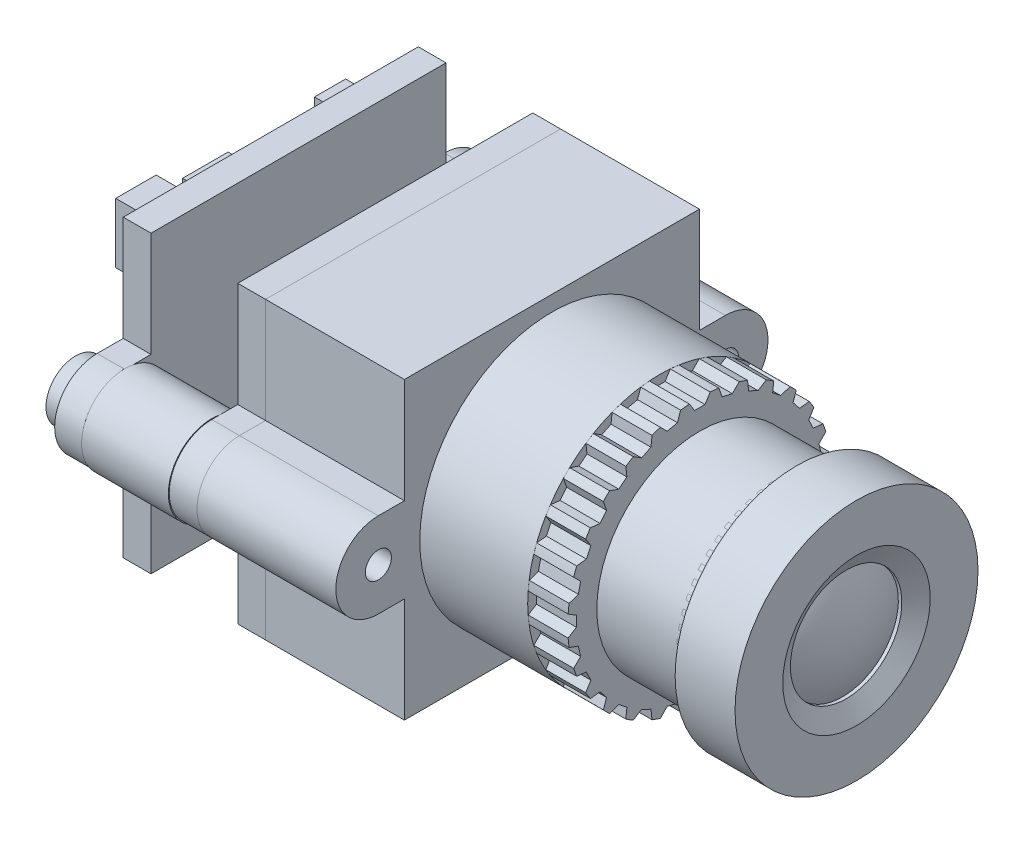
SolidWorks part; units mm, degrees
ref_plane "Front Plane" through (0, 0, 0) normal (0, 0, 1) x (1, 0, 0)
ref_plane "Top Plane" through (0, 0, 0) normal (0, 1, 0) x (1, 0, 0)
ref_plane "Right Plane" through (0, 0, 0) normal (1, 0, 0) x (0, 0, -1)
ref_axis "Axis1" through (-11.8965, 0, 0) along (1, 0, 0)
sketch "Sketch1" plane through (0, 0, 0) normal (1, 0, 0) x (0, 0, -1)
  circle A0 centre (0, 0) radius 7
  dimension "D1" = 14
extrude "Boss-Extrude1" add sketch "Sketch1" against normal blind 3.45
sketch "Sketch2" plane through (-3.45, 0, 0) normal (-1, 0, 0) x (0, 0, 1)
  circle A0 centre (0, 0) radius 5.935
  dimension "D1" = 11.87
extrude "Boss-Extrude2" add sketch "Sketch2" along normal blind 5.58
sketch "Sketch3" plane through (-9.03, 0, 0) normal (-1, 0, 0) x (0, 0, 1)
  circle A0 centre (0, 0) radius 7.61
  dimension "D1" = 15.22
extrude "Boss-Extrude3" add sketch "Sketch3" along normal blind 2.3
sketch "Sketch4" plane through (0, 0, 0) normal (0, 0, 1) x (1, 0, 0)
  line L0 (-3.45, 0) -> (0, 0) construction
  line L1 (-3.45, 5.935) -> (-3.45, -5.935) construction
  line L2 (0, -7) -> (0, 7) construction
  line L3 (0, 7) -> (-3.45, 7) construction
  line L4 (-0.6, 4.25) -> (0, 4.25)
  line L5 (-0.6, 4.25) -> (-0.6, -4.25)
  line L6 (-0.6, -4.25) -> (0, -4.25)
  line L7 (0, 4.25) -> (0, -4.25)
  line L8 (-0.6, 4.25) -> (0, -4.25) construction
  line L9 (-0.6, -4.25) -> (0, 4.25) construction
  line L10 (0, 4.25) -> (-0.6, 3.2108)
  line L11 (-0.8, 0) -> (-0.6, 3.2108) construction
  line L12 (-0.8, -3.2108) -> (-0.6, -3.2108)
  line L13 (-0.8, -3.2108) -> (-0.8, 3.2108)
  line L14 (-0.8, 3.2108) -> (-0.6, 3.2108)
  line L15 (-0.6, -3.2108) -> (-0.6, 3.2108)
  line L16 (-0.8, -3.2108) -> (-0.6, 3.2108) construction
  line L17 (-0.8, 3.2108) -> (-0.6, -3.2108) construction
  line L18 (-0.7, 1.6054) -> (0, 1.6054) construction
  line L19 (-0.8, 0) -> (0, 0)
  line L21 (0, 0) -> (0.6, 0)
  line L22 (0, 0) -> (0, 4.25)
  line L23 (0, 4.25) -> (0.6, 4.25)
  line L24 (0.6, 0) -> (0.6, 4.25)
  spline S0 degree 2 poles (0, 0) (0, 1.7034) (-0.8, 3.2108) knots 0 0 0 1 1 1
  point P6 (-0.3, 0)
  point P15 (-0.7, 0)
  dimension "D1" = 0.6
  dimension "D2" = 2.75
  dimension "D3" = 60
  dimension "D4" = 0.2
  dimension "D5" = 0.6
revolve "Cut-Revolve7" cut sketch "Sketch4" angle 360 about axis through (-11.8965, 0, 0) along (1, 0, 0) region at (0.3, 2.125, 0) region at (-0.2115, 2.72, 0) region at (-0.6658, 3.0768, 0)
sketch "Sketch5" plane through (-9.03, 0, 0) normal (1, 0, 0) x (0, 0, -1)
  line L0 (0, 7.61) -> (0, -7.61) construction
  line L1 (0.6, 7.5863) -> (0.3, 7.11)
  line L2 (0.3, 7.11) -> (-0.3, 7.11)
  line L3 (-0.6, 7.5863) -> (-0.3, 7.11)
  line L4 (2.2731, 7.2626) -> (1.8746, 6.865)
  line L5 (1.8746, 6.865) -> (1.2896, 6.9985)
  line L6 (1.1032, 7.5296) -> (1.2896, 6.9985)
  line L7 (3.8322, 6.5747) -> (3.3552, 6.2757)
  line L8 (3.3552, 6.2757) -> (2.8146, 6.5361)
  line L9 (2.751, 7.0954) -> (2.8146, 6.5361)
  line L10 (5.1991, 5.5571) -> (4.6676, 5.3718)
  line L11 (4.6676, 5.3718) -> (4.1985, 5.7459)
  line L12 (4.2609, 6.3053) -> (4.1985, 5.7459)
  line L13 (6.3053, 4.2609) -> (5.7459, 4.1985)
  line L14 (5.7459, 4.1985) -> (5.3718, 4.6676)
  line L15 (5.5571, 5.1991) -> (5.3718, 4.6676)
  line L16 (7.0954, 2.751) -> (6.5361, 2.8146)
  line L17 (6.5361, 2.8146) -> (6.2757, 3.3552)
  line L18 (6.5747, 3.8322) -> (6.2757, 3.3552)
  line L19 (7.5296, 1.1032) -> (6.9985, 1.2896)
  line L20 (6.9985, 1.2896) -> (6.865, 1.8746)
  line L21 (7.2626, 2.2731) -> (6.865, 1.8746)
  line L22 (7.5863, -0.6) -> (7.11, -0.3)
  line L23 (7.11, -0.3) -> (7.11, 0.3)
  line L24 (7.5863, 0.6) -> (7.11, 0.3)
  line L25 (7.2626, -2.2731) -> (6.865, -1.8746)
  line L26 (6.865, -1.8746) -> (6.9985, -1.2896)
  line L27 (7.5296, -1.1032) -> (6.9985, -1.2896)
  line L28 (6.5747, -3.8322) -> (6.2757, -3.3552)
  line L29 (6.2757, -3.3552) -> (6.5361, -2.8146)
  line L30 (7.0954, -2.751) -> (6.5361, -2.8146)
  line L31 (5.5571, -5.1991) -> (5.3718, -4.6676)
  line L32 (5.3718, -4.6676) -> (5.7459, -4.1985)
  line L33 (6.3053, -4.2609) -> (5.7459, -4.1985)
  line L34 (4.2609, -6.3053) -> (4.1985, -5.7459)
  line L35 (4.1985, -5.7459) -> (4.6676, -5.3718)
  line L36 (5.1991, -5.5571) -> (4.6676, -5.3718)
  line L37 (2.751, -7.0954) -> (2.8146, -6.5361)
  line L38 (2.8146, -6.5361) -> (3.3552, -6.2757)
  line L39 (3.8322, -6.5747) -> (3.3552, -6.2757)
  line L40 (1.1032, -7.5296) -> (1.2896, -6.9985)
  line L41 (1.2896, -6.9985) -> (1.8746, -6.865)
  line L42 (2.2731, -7.2626) -> (1.8746, -6.865)
  line L43 (-0.6, -7.5863) -> (-0.3, -7.11)
  line L44 (-0.3, -7.11) -> (0.3, -7.11)
  line L45 (0.6, -7.5863) -> (0.3, -7.11)
  line L46 (-2.2731, -7.2626) -> (-1.8746, -6.865)
  line L47 (-1.8746, -6.865) -> (-1.2896, -6.9985)
  line L48 (-1.1032, -7.5296) -> (-1.2896, -6.9985)
  line L49 (-3.8322, -6.5747) -> (-3.3552, -6.2757)
  line L50 (-3.3552, -6.2757) -> (-2.8146, -6.5361)
  line L51 (-2.751, -7.0954) -> (-2.8146, -6.5361)
  line L52 (-5.1991, -5.5571) -> (-4.6676, -5.3718)
  line L53 (-4.6676, -5.3718) -> (-4.1985, -5.7459)
  line L54 (-4.2609, -6.3053) -> (-4.1985, -5.7459)
  line L55 (-6.3053, -4.2609) -> (-5.7459, -4.1985)
  line L56 (-5.7459, -4.1985) -> (-5.3718, -4.6676)
  line L57 (-5.5571, -5.1991) -> (-5.3718, -4.6676)
  line L58 (-7.0954, -2.751) -> (-6.5361, -2.8146)
  line L59 (-6.5361, -2.8146) -> (-6.2757, -3.3552)
  line L60 (-6.5747, -3.8322) -> (-6.2757, -3.3552)
  line L61 (-7.5296, -1.1032) -> (-6.9985, -1.2896)
  line L62 (-6.9985, -1.2896) -> (-6.865, -1.8746)
  line L63 (-7.2626, -2.2731) -> (-6.865, -1.8746)
  line L64 (-7.5863, 0.6) -> (-7.11, 0.3)
  line L65 (-7.11, 0.3) -> (-7.11, -0.3)
  line L66 (-7.5863, -0.6) -> (-7.11, -0.3)
  line L67 (-7.2626, 2.2731) -> (-6.865, 1.8746)
  line L68 (-6.865, 1.8746) -> (-6.9985, 1.2896)
  line L69 (-7.5296, 1.1032) -> (-6.9985, 1.2896)
  line L70 (-6.5747, 3.8322) -> (-6.2757, 3.3552)
  line L71 (-6.2757, 3.3552) -> (-6.5361, 2.8146)
  line L72 (-7.0954, 2.751) -> (-6.5361, 2.8146)
  line L73 (-5.5571, 5.1991) -> (-5.3718, 4.6676)
  line L74 (-5.3718, 4.6676) -> (-5.7459, 4.1985)
  line L75 (-6.3053, 4.2609) -> (-5.7459, 4.1985)
  line L76 (-4.2609, 6.3053) -> (-4.1985, 5.7459)
  line L77 (-4.1985, 5.7459) -> (-4.6676, 5.3718)
  line L78 (-5.1991, 5.5571) -> (-4.6676, 5.3718)
  line L79 (-2.751, 7.0954) -> (-2.8146, 6.5361)
  line L80 (-2.8146, 6.5361) -> (-3.3552, 6.2757)
  line L81 (-3.8322, 6.5747) -> (-3.3552, 6.2757)
  line L82 (-1.1032, 7.5296) -> (-1.2896, 6.9985)
  line L83 (-1.2896, 6.9985) -> (-1.8746, 6.865)
  line L84 (-2.2731, 7.2626) -> (-1.8746, 6.865)
  circle A0 centre (0, 0) radius 7.61 construction
  circle A1 centre (0, 0) radius 7.61 construction
  circle A2 centre (0, 0) radius 7.61
  point P12 (0, 7.11)
  point P123 (0, 0)
  circle M6 centre (0, 0) radius 7.61
  dimension "D1" = 0.6
  dimension "D2" = 1.2
  dimension "D3" = 0.5
  dimension "D5" = 0.5063
  dimension "D4" = 28
extrude "Cut-Extrude1" cut sketch "Sketch5" against normal up to next (2.3 mm away) contours L9 L8 L7 M6 | L6 L5 L4 M6 | L0 L2 L1 M6 | L84 L83 L82 M6 | L0 A2 L3 L2 | L81 L80 L79 M6 | L78 L77 L76 M6 | L75 L74 L73 M6 | L72 L71 L70 M6 | L69 L68 L67 M6 | L66 L65 L64 M6 | L63 L62 L61 M6 | L60 L59 L58 M6 | L57 L56 L55 M6 | L51 L50 L49 M6 | L54 L53 L52 M6 | L48 L47 L46 M6 | L0 L44 L43 M6 | L44 L0 A2 L45 | L42 L41 L40 M6 | L39 L38 L37 M6 | L36 L35 L34 M6 | L33 L32 L31 M6 | L30 L29 L28 M6 | L27 L26 L25 M6 | L24 L23 L22 M6 | L21 L20 L19 M6 | L18 L17 L16 M6 | L15 L14 L13 M6 | L12 L11 L10 M6 region at (-9.03, 7.384, -0.233) region at (-9.03, 7.384, 0.233) region at (-9.03, -7.384, -0.233) region at (-9.03, -7.384, 0.233) region at (-9.03, 7.1989, -1.6431) region at (-9.03, 7.1989, 1.6431) region at (-9.03, 6.6527, -3.2038) region at (-9.03, 6.6527, 3.2038) region at (-9.03, -7.1989, 1.6431) region at (-9.03, -7.1989, -1.6431) region at (-9.03, 5.773, -4.6038) region at (-9.03, 5.773, 4.6038) region at (-9.03, -6.6527, 3.2038) region at (-9.03, -6.6527, -3.2038) region at (-9.03, 4.6038, -5.773) region at (-9.03, 4.6038, 5.773) region at (-9.03, -5.773, 4.6038) region at (-9.03, -5.773, -4.6038) region at (-9.03, 3.2038, -6.6527) region at (-9.03, 3.2038, 6.6527) region at (-9.03, -4.6038, 5.773) region at (-9.03, -4.6038, -5.773) region at (-9.03, 1.6431, -7.1989) region at (-9.03, 1.6431, 7.1989) region at (-9.03, -3.2038, 6.6527) region at (-9.03, -3.2038, -6.6527) region at (-9.03, 0, -7.384) region at (-9.03, 0, 7.384) region at (-9.03, -1.6431, 7.1989) region at (-9.03, -1.6431, -7.1989)
sketch "Sketch6" plane through (-11.33, 0, 0) normal (-1, 0, 0) x (0, 0, 1)
  line L0 (0, 7.615) -> (0, -7.615) construction
  line L2 (-8.5, -8.5) -> (8.5, -8.5)
  line L3 (-8.5, -8.5) -> (-8.5, 8.5)
  line L4 (-8.5, 8.5) -> (8.5, 8.5)
  line L5 (8.5, -8.5) -> (8.5, 8.5)
  line L6 (-8.5, -8.5) -> (8.5, 8.5) construction
  line L7 (-8.5, 8.5) -> (8.5, -8.5) construction
  line L8 (-1.25, -7.5117) -> (1.25, -7.5117)
  line L9 (-1.25, -7.5117) -> (-1.25, -8.5)
  line L10 (-1.25, -8.5) -> (1.25, -8.5)
  line L11 (1.25, -7.5117) -> (1.25, -8.5)
  line L12 (-1.25, -7.5117) -> (1.25, -8.5) construction
  line L13 (-1.25, -8.5) -> (1.25, -7.5117) construction
  circle A0 centre (0, 0) radius 7.615
  point P9 (0, -8.0059)
  dimension "D1" = 15.23
  dimension "D2" = 17
  dimension "D3" = 2.5
extrude "Boss-Extrude4" add sketch "Sketch6" along normal offset from surface (6.22 mm away) 17.55 contours A0 L9 L2 L11 | A0 region at (-11.33, -8.0398, 0) up to face at (0, 0, 4.25)
sketch "Sketch7" plane through (-17.55, 0, 0) normal (-1, 0, 0) x (0, 0, 1)
  line L0 (1.25, -8.5) -> (-1.25, -8.5) construction
  line L1 (-8.5, -8.5) -> (8.5, -8.5)
  line L2 (-8.5, -8.5) -> (-8.5, 8.5)
  line L3 (-8.5, 8.5) -> (8.5, 8.5)
  line L4 (8.5, -8.5) -> (8.5, 8.5)
  line L5 (-8.5, -8.5) -> (8.5, 8.5) construction
  line L6 (-8.5, 8.5) -> (8.5, -8.5) construction
  line L7 (-8.5, 0) -> (8.5, 0) construction
  line L8 (0, 8.5) -> (0, -8.5) construction
  line L9 (-10, 2.45) -> (-8.5, 2.45)
  line L10 (-10, -2.45) -> (-8.5, -2.45)
  line L11 (10, 2.45) -> (8.5, 2.45)
  line L12 (10, -2.45) -> (8.5, -2.45)
  circle A0 centre (-10, 0) radius 2.45
  circle A1 centre (-10, 0) radius 0.75
  circle A2 centre (10, 0) radius 0.75
  circle A3 centre (10, 0) radius 2.45
  point P0 (0, 0)
  dimension "D1" = 4.9
  dimension "D3" = 1.5
  dimension "D2" = 20
extrude "Boss-Extrude5" add sketch "Sketch7" along normal blind 8 contours A0 L10 L2 | L2 A0 A1 | A0 L2 L9 | L12 A3 L4 | A3 L4 A2 | L4 A3 L11 | L1 L4 L3 L2 region at (-17.55, -2.2994, -8.8667) region at (-17.55, -2.2994, 8.8667) region at (-17.55, -2.2587, -9.2277) region at (-17.55, 0, 8.5629) region at (-17.55, 2.2994, -8.8667) region at (-17.55, 2.2994, 8.8667)
sketch "Sketch8" plane through (-25.55, 0, 0) normal (-1, 0, 0) x (0, 0, 1)
  line L10 (-10, -2.45) -> (-8.5, -2.45)
  line L11 (-8.5, -2.45) -> (-8.5, -8.5)
  line L12 (-8.5, -8.5) -> (8.5, -8.5)
  line L13 (8.5, -8.5) -> (8.5, -2.45)
  line L14 (8.5, -2.45) -> (10, -2.45)
  line L15 (10, 2.45) -> (8.5, 2.45)
  line L16 (8.5, 2.45) -> (8.5, 8.5)
  line L17 (8.5, 8.5) -> (-8.5, 8.5)
  line L18 (-8.5, 8.5) -> (-8.5, 2.45)
  line L19 (-8.5, 2.45) -> (-10, 2.45)
  line L20 (-10, -2.45) -> (-8.5, -2.45)
  line L21 (-8.5, -2.45) -> (-8.5, -8.5)
  line L22 (-8.5, -8.5) -> (8.5, -8.5)
  line L23 (8.5, -8.5) -> (8.5, -2.45)
  line L24 (8.5, -2.45) -> (10, -2.45)
  line L25 (10, 2.45) -> (8.5, 2.45)
  line L26 (8.5, 2.45) -> (8.5, 8.5)
  line L27 (8.5, 8.5) -> (-8.5, 8.5)
  line L28 (-8.5, 8.5) -> (-8.5, 2.45)
  line L29 (-8.5, 2.45) -> (-10, 2.45)
  circle A0 centre (10, 0) radius 0.75 construction
  circle A1 centre (-10, 0) radius 0.75 construction
  arc A2 (10, -2.45) -> (10, 2.45) centre (10, 0) ccw
  arc A3 (-10, 2.45) -> (-10, -2.45) centre (-10, 0) ccw
  arc A4 (10, -2.45) -> (10, 2.45) centre (10, 0) ccw
  arc A5 (-10, 2.45) -> (-10, -2.45) centre (-10, 0) ccw
  circle A6 centre (10, 0) radius 0.75
  circle A7 centre (-10, 0) radius 0.75
  dimension "D1" = 0
extrude "Boss-Extrude6" add sketch "Sketch8" along normal blind 1.6 separate body
sketch "Sketch9" plane through (-27.15, 0, 0) normal (-1, 0, 0) x (0, 0, 1)
  line L0 (0, 8.5) -> (0, -8.5) construction
  line L1 (8.5, 8.5) -> (-8.5, 8.5) construction
  line L2 (-8.5, -8.5) -> (8.5, -8.5) construction
  circle A0 centre (-10, 0) radius 2.5
  circle A1 centre (-10, 0) radius 1
  circle A2 centre (10, 0) radius 2.5
  circle A3 centre (10, 0) radius 1
  dimension "D1" = 5
  dimension "D2" = 2
extrude "Boss-Extrude7" add sketch "Sketch9" along normal blind 5 separate body
sketch "Sketch10" plane through (-32.15, 0, 0) normal (-1, 0, 0) x (0, 0, 1)
  line L10 (-10, -2.45) -> (-8.5, -2.45)
  line L11 (-8.5, -2.45) -> (-8.5, -8.5)
  line L12 (-8.5, -8.5) -> (8.5, -8.5)
  line L13 (8.5, -8.5) -> (8.5, -2.45)
  line L14 (8.5, -2.45) -> (10, -2.45)
  line L15 (10, 2.45) -> (8.5, 2.45)
  line L16 (8.5, 2.45) -> (8.5, 8.5)
  line L17 (8.5, 8.5) -> (-8.5, 8.5)
  line L18 (-8.5, 8.5) -> (-8.5, 2.45)
  line L19 (-8.5, 2.45) -> (-10, 2.45)
  line L20 (-10, -2.45) -> (-8.5, -2.45)
  line L21 (-8.5, -2.45) -> (-8.5, -8.5)
  line L22 (-8.5, -8.5) -> (8.5, -8.5)
  line L23 (8.5, -8.5) -> (8.5, -2.45)
  line L24 (8.5, -2.45) -> (10, -2.45)
  line L25 (10, 2.45) -> (8.5, 2.45)
  line L26 (8.5, 2.45) -> (8.5, 8.5)
  line L27 (8.5, 8.5) -> (-8.5, 8.5)
  line L28 (-8.5, 8.5) -> (-8.5, 2.45)
  line L29 (-8.5, 2.45) -> (-10, 2.45)
  circle A0 centre (-10, 0) radius 0.75 construction
  circle A1 centre (10, 0) radius 0.75 construction
  arc A2 (-10, 2.45) -> (-10, -2.45) centre (-10, 0) ccw
  arc A3 (10, -2.45) -> (10, 2.45) centre (10, 0) ccw
  arc A4 (-10, 2.45) -> (-10, -2.45) centre (-10, 0) ccw
  arc A5 (10, -2.45) -> (10, 2.45) centre (10, 0) ccw
  circle A6 centre (10, 0) radius 0.75
  circle A7 centre (-10, 0) radius 0.75
  dimension "D1" = 0
extrude "Boss-Extrude8" add sketch "Sketch10" along normal blind 1.6 separate body
sketch "Sketch11" plane through (-33.75, 0, 0) normal (-1, 0, 0) x (0, 0, 1)
  line L0 (0, 8.5) -> (0, -8.5) construction
  line L1 (8.5, 8.5) -> (-8.5, 8.5) construction
  line L2 (-8.5, -8.5) -> (8.5, -8.5) construction
  line L4 (-3.5, -4.7) -> (3.5, -4.7)
  line L5 (-3.5, -4.7) -> (-3.5, -7.9)
  line L6 (-3.5, -7.9) -> (3.5, -7.9)
  line L7 (3.5, -4.7) -> (3.5, -7.9)
  line L8 (-3.5, -4.7) -> (3.5, -7.9) construction
  line L9 (-3.5, -7.9) -> (3.5, -4.7) construction
  point P6 (0, -6.3)
  dimension "D1" = 7
  dimension "D2" = 3.2
  dimension "D3" = 0.6
extrude "Boss-Extrude9" add sketch "Sketch11" along normal blind 4.8 separate body
sketch "Sketch12" plane through (-38.55, 0, 0) normal (-1, 0, 0) x (0, 0, 1)
  line L0 (-3.5, -4.7) -> (3.5, -7.9) construction
  line L1 (3.5, -7.9) -> (3.5, -4.7) construction
  line L2 (-3.15, -7.55) -> (3.15, -7.55)
  line L3 (-3.15, -7.55) -> (-3.15, -5.05)
  line L4 (-3.15, -5.05) -> (3.15, -5.05)
  line L5 (3.15, -7.55) -> (3.15, -5.05)
  line L6 (-3.15, -7.55) -> (3.15, -5.05) construction
  line L7 (-3.15, -5.05) -> (3.15, -7.55) construction
  line L8 (3.15, -5.05) -> (3.5, -5.05) construction
  line L9 (3.15, -5.05) -> (3.15, -4.7) construction
  line L10 (3.5, -4.7) -> (-3.5, -4.7) construction
  point P4 (0, -6.3)
  dimension "D1" = 0.35
extrude "Cut-Extrude2" cut sketch "Sketch12" against normal offset from surface (4.4 mm away) 0.4 up to face at (-33.75, 0, 10.75)
sketch "Sketch13" plane through (-38.55, 0, 0) normal (-1, 0, 0) x (0, 0, 1)
  line L0 (0, -5.05) -> (0, -4.7) construction
  line L1 (3.15, -5.05) -> (-3.15, -5.05) construction
  line L2 (3.5, -4.7) -> (-3.5, -4.7) construction
  line L4 (-2.4, -5.05) -> (2.4, -5.05)
  line L5 (-2.4, -5.05) -> (-2.4, -4.7)
  line L6 (-2.4, -4.7) -> (2.4, -4.7)
  line L7 (2.4, -5.05) -> (2.4, -4.7)
  line L8 (-2.4, -5.05) -> (2.4, -4.7) construction
  line L9 (-2.4, -4.7) -> (2.4, -5.05) construction
  point P6 (0, -4.875)
  dimension "D1" = 4.8
extrude "Cut-Extrude3" cut sketch "Sketch13" against normal blind 1.5
sketch "Sketch14" plane through (-33.75, 0, 0) normal (-1, 0, 0) x (0, 0, 1)
  line L1 (6.733, 7.4544) -> (4.4023, 7.4544)
  line L2 (6.733, 7.4544) -> (6.733, 3.9954)
  line L3 (6.733, 3.9954) -> (4.4023, 3.9954)
  line L4 (4.4023, 7.4544) -> (4.4023, 3.9954)
  line L5 (3.6255, -8.0463) -> (5.9191, -8.0463)
  line L6 (3.6255, -8.0463) -> (3.6255, -4.1064)
  line L7 (3.6255, -4.1064) -> (5.9191, -4.1064)
  line L8 (5.9191, -8.0463) -> (5.9191, -4.1064)
  line L9 (-2.5526, -1.9607) -> (-0.9249, -1.9607)
  line L10 (-2.5526, -1.9607) -> (-2.5526, -3.8844)
  line L11 (-2.5526, -3.8844) -> (-0.9249, -3.8844)
  line L12 (-0.9249, -1.9607) -> (-0.9249, -3.8844)
  line L13 (-3.4035, 2.1827) -> (0.8694, 2.1827)
  line L14 (-3.4035, 2.1827) -> (-3.4035, 0.222)
  line L15 (-3.4035, 0.222) -> (0.8694, 0.222)
  line L16 (0.8694, 2.1827) -> (0.8694, 0.222)
  line L17 (-6.511, 6.7885) -> (-4.7168, 6.7885)
  line L18 (-6.511, 6.7885) -> (-6.511, 3.9954)
  line L19 (-6.511, 3.9954) -> (-4.7168, 3.9954)
  line L20 (-4.7168, 6.7885) -> (-4.7168, 3.9954)
  line L21 (0.259, 6.5295) -> (2.8856, 6.5295)
  line L22 (0.259, 6.5295) -> (0.259, 5.1977)
  line L23 (0.259, 5.1977) -> (2.8856, 5.1977)
  line L24 (2.8856, 6.5295) -> (2.8856, 5.1977)
extrude "Boss-Extrude10" add sketch "Sketch14" along normal blind 2.2
sketch "Sketch15" plane through (-33.75, 0, 0) normal (-1, 0, 0) x (0, 0, 1)
  circle A0 centre (-10, 0) radius 1.7
  circle A1 centre (10, 0) radius 1.7
  dimension "D1" = 3.4
extrude "Boss-Extrude11" add sketch "Sketch15" along normal blind 1.25
sketch "Sketch16" plane through (-3.45, 0, 0) normal (-1, 0, 0) x (0, 0, 1)
  circle A0 centre (0, 0) radius 5.935 construction
  circle A1 centre (0, 0) radius 5.935
extrude "Boss-Extrude12" add sketch "Sketch16" along normal blind 1 separate body
ref_axis "Axis2" through (-40.4775, 0, 0) along (1, 0, 0)
ref_plane "Plane1" through (10, 0, 0) normal (1, 0, 0) x (0, 0, -1)
ref_plane "Plane2" through (-3.45, 0, 0) normal (-1, 0, 0) x (0, 0, 1)
ref_point "Camera position"
ref_point "Camera target"
